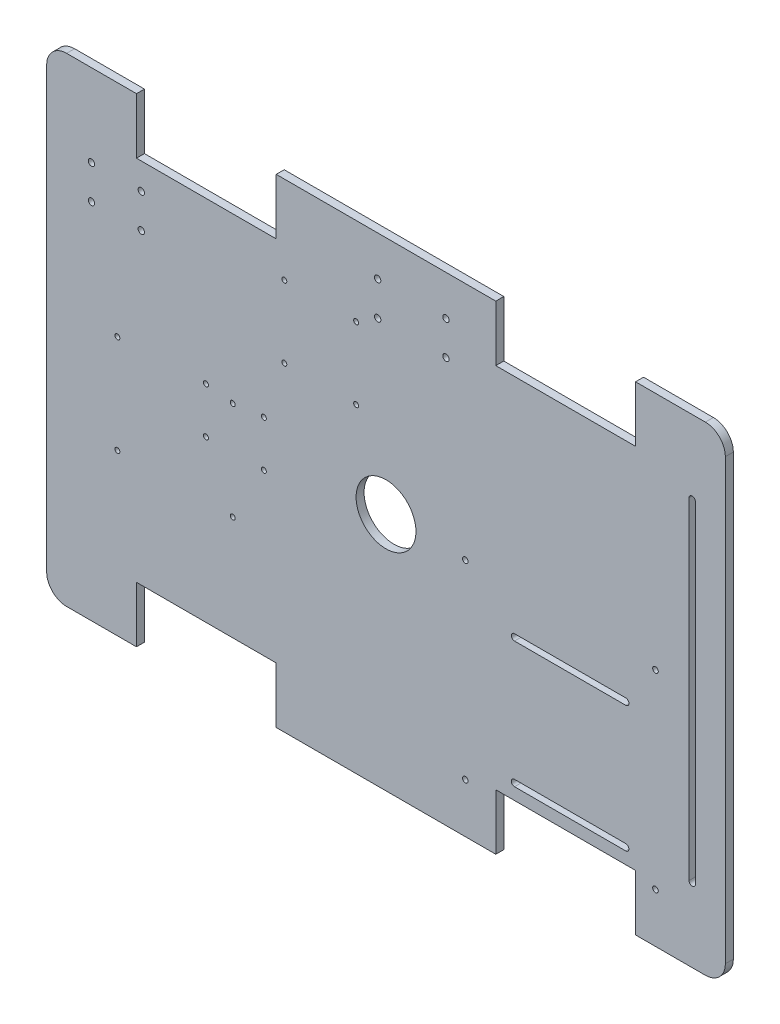
SolidWorks part; units mm, degrees
ref_plane "前视基准面" through (0, 0, 0) normal (0, 0, 1) x (1, 0, 0)
ref_plane "上视基准面" through (0, 0, 0) normal (0, 1, 0) x (1, 0, 0)
ref_plane "右视基准面" through (0, 0, 0) normal (1, 0, 0) x (0, 0, -1)
other "Configuration Table"
sketch "草图1" plane through (0, 0, 0) normal (0, 0, 1) x (1, 0, 0)
  line L0 (-232.03, 0) -> (-100.2513, 0) construction
  line L1 (160, -120) -> (-160, -120)
  line L2 (170, -110) -> (170, 110)
  line L3 (160, 120) -> (-160, 120)
  line L4 (-170, -110) -> (-170, 110)
  line L5 (170, -120) -> (-170, 120) construction
  line L6 (170, 120) -> (-170, -120) construction
  line L7 (0, -161.7122) -> (0, 250.7886) construction
  line L8 (0, 0) -> (270.6764, 0) construction
  line L9 (-110, 120) -> (-110, 44)
  line L10 (-170, 103) -> (-110, 103) construction
  line L11 (-110, 44) -> (-70, 44)
  line L12 (-70, 44) -> (-70, 120)
  line L17 (-100.2513, 0) -> (0, 0) construction
  line L18 (-76.2884, 0) -> (-76.2884, 20.8877) construction
  line L19 (-76.2884, 4.5) -> (-76.2884, -4.5) construction
  line L21 (39.75, 0) -> (135, 0)
  line L23 (151.8, -83) -> (151.8, 83)
  line L26 (155, 83) -> (155, -83)
  line L27 (-98.3572, 33.5299) -> (-98.3572, -40.4701)
  line L28 (104.4374, 33.5299) -> (-144.6743, 33.5299) construction
  line L30 (39.75, 0) -> (39.75, -95.25)
  circle A20 centre (-105, 76) radius 1.75
  circle A21 centre (-75, 76) radius 1.75
  circle A22 centre (-75, 52) radius 1.75
  circle A23 centre (-105, 52) radius 1.75
  circle A24 centre (-105, 76) radius 1.75
  circle A25 centre (-75, 76) radius 1.75
  circle A26 centre (-75, 52) radius 1.75
  circle A27 centre (-105, 52) radius 1.75
  circle A40 centre (-90.2053, 11.5) radius 1.25
  arc A43 (151.8, 83) -> (155, 83) centre (153.4, 83) cw
  arc A44 (151.8, -83) -> (155, -83) centre (153.4, -83) ccw
  circle A45 centre (0, 0) radius 15
  arc A46 (170, 110) -> (160, 120) centre (160, 110) ccw
  arc A47 (160, -120) -> (170, -110) centre (160, -110) ccw
  circle A48 centre (135, -95.25) radius 1.4
  circle A49 centre (39.75, -95.25) radius 1.4
  circle A50 centre (135, 0) radius 1.4
  circle A51 centre (39.75, 0) radius 1.4
  arc A52 (-160, -120) -> (-170, -110) centre (-160, -110) cw
  arc A53 (-170, 110) -> (-160, 120) centre (-160, 110) cw
  circle A54 centre (75, 76) radius 1.75
  circle A55 centre (75, 52) radius 1.75
  circle A56 centre (105, 52) radius 1.75
  circle A57 centre (105, 76) radius 1.75
  circle A58 centre (75, -76) radius 1.75
  circle A59 centre (75, -52) radius 1.75
  circle A60 centre (105, -52) radius 1.75
  circle A61 centre (105, -76) radius 1.75
  circle A62 centre (-105, -52) radius 1.75
  circle A63 centre (-75, -52) radius 1.75
  circle A64 centre (-75, -76) radius 1.75
  circle A65 centre (-105, -76) radius 1.75
  point P0 (0, 0)
  point P52 (-85.7513, 0)
  point P60 (155, 0)
  point P65 (-151.1375, 0)
  point P71 (151.8, 0)
  dimension "D5" = 3.5
  dimension "D6" = 3.5
  dimension "D7" = 3.5
  dimension "D15" = 15
  dimension "D18" = 30
  dimension "D19" = 2.5
  dimension "D20" = 2.8
  dimension "D22" = 2.8
  dimension "D23" = 2.8
  dimension "D24" = 2.8
  dimension "D25" = 95.25
  dimension "D28" = 95.25
  dimension "D30" = 35
  dimension "D31" = 10
  dimension "D32" = 8
  dimension "D33" = 24
  dimension "D34" = 24
  dimension "D35" = 8
  dimension "D36" = 3.5
  dimension "D1" = 240
  dimension "D2" = 340
  dimension "D3" = 60
  dimension "D4" = 76
  dimension "D8" = 40
  dimension "D9" = 5
  dimension "D10" = 5
  dimension "D11" = 5
  dimension "D12" = 5
  dimension "D13" = 60
  dimension "D14" = 3.2
  dimension "D16" = 3.2
  dimension "D17" = 16.6
  dimension "D21" = 74
  dimension "D26" = 95.25
  dimension "D27" = 95.25
  dimension "D29" = 90
extrude "凸台-拉伸1" add sketch "草图1" along normal blind 4 contours L3 A53 L4 A52 L1 A47 L2 A46
extrude "切除-拉伸4" cut sketch "草图1<4>" along normal blind 10 contours A40
sketch "草图1<4>" plane through (0, 0, 0) normal (0, 0, 1) x (1, 0, 0) same geometry as "草图1"
pattern_linear "阵列(线性)1" count 2 spacing 29 along (1, 0, 0) count 2 spacing 23 along (0, -1, 0) of "切除-拉伸4"
extrude "切除-拉伸6" cut sketch "草图1<6>" along normal blind 19 contours L26 A44 L23 A43
sketch "草图1<6>" plane through (0, 0, 0) normal (0, 0, 1) x (1, 0, 0) same geometry as "草图1"
extrude "切除-拉伸8" cut sketch "草图1<7>" along normal blind 9 contours A48 | A49 | A50 | A51
sketch "草图1<7>" plane through (0, 0, 0) normal (0, 0, 1) x (1, 0, 0) same geometry as "草图1"
extrude "切除-拉伸12" cut sketch "草图1<8>" along normal blind 9 contours A45
sketch "草图1<8>" plane through (0, 0, 0) normal (0, 0, 1) x (1, 0, 0) same geometry as "草图1"
sketch "草图4" plane through (0, 0, 0) normal (0, 0, -1) x (-1, 0, 0)
  line L0 (-46.0096, 91.5) -> (-2.581, 91.5) construction
  line L1 (-12.9235, 91.5) -> (-12.9235, 112.5994) construction
  line L2 (-12.9235, 110) -> (-12.9235, 73) construction
  line L3 (115.5765, 87.8299) -> (115.5765, 52.8299) construction
  line L6 (135.0753, 80.1712) -> (135.0753, 56.5299) construction
  line L7 (135.0753, 70.3299) -> (135.0753, 99.0131) construction
  line L8 (135.0753, 99.0131) -> (135.0753, 36.4843) construction
  line L9 (146.6671, 56.5299) -> (118.7666, 56.5299) construction
  line L10 (115.5765, 70.3299) -> (154.5741, 70.3299) construction
  line L11 (154.5741, 87.8299) -> (154.5741, 52.8299) construction
  circle A0 centre (-30.0235, 100) radius 1.6
  circle A1 centre (4.1765, 100) radius 1.6
  circle A2 centre (4.1765, 83) radius 1.6
  circle A3 centre (-30.0235, 83) radius 1.6
  circle A8 centre (122.5939, 78.8299) radius 1.5983
  circle A9 centre (147.5567, 78.8299) radius 1.5983
  circle A10 centre (122.5939, 61.8299) radius 1.5983
  circle A11 centre (147.5567, 61.8299) radius 1.5983
  dimension "D1" = 17
  dimension "D2" = 3.1966
extrude "切除-拉伸14" cut sketch "草图4" against normal blind 10
sketch "草图5" plane through (0, 0, 4) normal (0, 0, 1) x (1, 0, 0)
  line L0 (-70, 82) -> (-113.1965, 82) construction
  line L1 (-70, 44) -> (-70, 120) construction
  line L2 (-90, 44) -> (-90, 119.3784) construction
  line L3 (-110, 44) -> (-70, 44) construction
  line L4 (160, 120) -> (-160, 120) construction
  line L5 (-55, 120) -> (-125, 120)
  line L6 (-55, 120) -> (-55, 44)
  line L7 (-55, 44) -> (-125, 44)
  line L8 (-125, 120) -> (-125, 44)
  line L9 (-55, 120) -> (-125, 44) construction
  line L10 (-55, 44) -> (-125, 120) construction
  line L11 (0, 0) -> (0, 13.06) construction
  line L12 (0, -161.7122) -> (0, 250.7886) construction
  line L13 (0, 0) -> (13.8084, 0) construction
  line L14 (0, 0) -> (270.6764, 0) construction
  line L15 (55, 44) -> (125, 44)
  line L16 (125, 120) -> (125, 44)
  line L17 (55, 120) -> (125, 120)
  line L18 (55, 120) -> (55, 44)
  line L19 (55, -120) -> (55, -44)
  line L20 (55, -120) -> (125, -120)
  line L21 (125, -120) -> (125, -44)
  line L22 (55, -44) -> (125, -44)
  line L23 (-55, -44) -> (-125, -44)
  line L24 (-125, -120) -> (-125, -44)
  line L25 (-55, -120) -> (-125, -120)
  line L26 (-55, -120) -> (-55, -44)
  line L27 (-125, 92) -> (-55, 92)
  line L28 (125, 92) -> (55, 92)
  line L29 (125, -92) -> (55, -92)
  line L30 (-125, -92) -> (-55, -92)
  line L31 (90, 92) -> (90, 138.4685) construction
  point P8 (-90, 82)
  line M24 (160, 120) -> (-160, 120)
  line M28 (-160, -120) -> (160, -120)
  dimension "D1" = 0
  dimension "D2" = 35
  dimension "D3" = 28
extrude "切除-拉伸15" cut sketch "草图5" against normal blind 10 contours L8 L27 L6 M24 region at (-90, 106, 4)
extrude "切除-拉伸16" cut sketch "草图5<3>" against normal blind 10 contours L28 L16 L18 M24 | L21 L29 L19 M28 | L30 L24 L26 M28 region at (90, 106, 4) region at (90, -106, 4) region at (-90, -106, 4)
sketch "草图5<3>" plane through (0, 0, 4) normal (0, 0, 1) x (1, 0, 0) same geometry as "草图5"
sketch "草图7" plane through (0, 0, 4) normal (0, 0, 1) x (1, 0, 0)
  line L0 (64.3724, -82.8) -> (120.0874, -82.8)
  line L1 (92.2299, -82.8) -> (92.2299, -22.8) construction
  line L3 (120.0874, -86) -> (64.3724, -86)
  line L5 (118.4874, -84.4) -> (120.0874, -84.4)
  line L6 (160, -120) -> (-160, -120) construction
  line L7 (92.2299, -52.8) -> (-60.1857, -52.8) construction
  line L8 (64.3724, -22.8) -> (120.0874, -22.8)
  line L9 (120.0874, -19.6) -> (64.3724, -19.6)
  arc A0 (64.3724, -82.8) -> (64.3724, -86) centre (64.3724, -84.4) ccw
  arc A1 (120.0874, -86) -> (120.0874, -82.8) centre (120.0874, -84.4) ccw
  arc A2 (120.0874, -19.6) -> (120.0874, -22.8) centre (120.0874, -21.2) cw
  arc A3 (64.3724, -22.8) -> (64.3724, -19.6) centre (64.3724, -21.2) cw
  dimension "D3" = 1.6
  dimension "D5" = 1.6
  dimension "D1" = 3.2
  dimension "D2" = 1.6
  dimension "D4" = 34
  dimension "D6" = 60
extrude "切除-拉伸17" cut sketch "草图7" against normal blind 10 contours L0 A1 L3 A0 | L9 A3 L8 A2
sketch "草图8" plane through (0, 0, 0) normal (0, 0, -1) x (-1, 0, 0)
  circle A0 centre (14.9577, 76.1171) radius 1.25
  circle A1 centre (50.9577, 76.1171) radius 1.25
  circle A2 centre (50.9577, 40.1171) radius 1.2486
  circle A3 centre (14.9577, 40.1171) radius 1.246
  circle A4 centre (134.5765, -39.5672) radius 1.25
  circle A5 centre (134.5765, 9.7328) radius 1.25
  circle A6 centre (76.7765, 9.7328) radius 1.25
  circle A7 centre (76.7765, -39.5672) radius 1.25
  dimension "D1" = 2.5
  dimension "D2" = 2.4999
  dimension "D3" = 2.4973
  dimension "D4" = 2.492
  dimension "D5" = 2.5
  dimension "D6" = 2.5
  dimension "D7" = 2.5
  dimension "D8" = 2.5
extrude "切除-拉伸18" cut sketch "草图8" against normal blind 10
